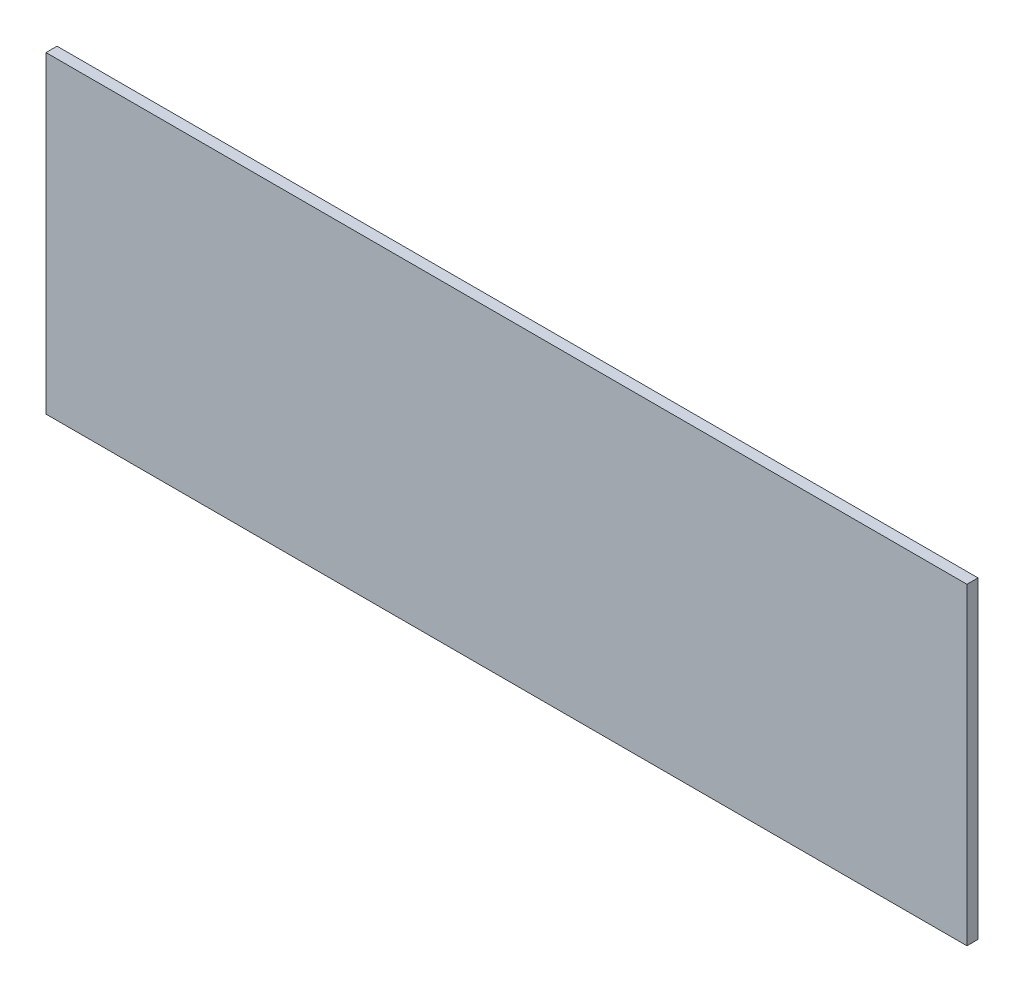
SolidWorks part; units mm, degrees
ref_plane "Front Plane" through (0, 0, 0) normal (0, 0, 1) x (1, 0, 0)
ref_plane "Top Plane" through (0, 0, 0) normal (0, 1, 0) x (1, 0, 0)
ref_plane "Right Plane" through (0, 0, 0) normal (1, 0, 0) x (0, 0, -1)
sketch "Sketch1" plane through (0, 0, 0) normal (0, 0, 1) x (1, 0, 0)
  line L1 (-125, 42.5) -> (125, 42.5)
  line L2 (-125, 42.5) -> (-125, -42.5)
  line L3 (-125, -42.5) -> (125, -42.5)
  line L4 (125, 42.5) -> (125, -42.5)
  line L5 (-125, 42.5) -> (125, -42.5) construction
  line L6 (-125, -42.5) -> (125, 42.5) construction
  point P0 (0, 0)
  dimension "D1" = 85
  dimension "D2" = 250
extrude "Boss-Extrude1" add sketch "Sketch1" along normal blind 3
